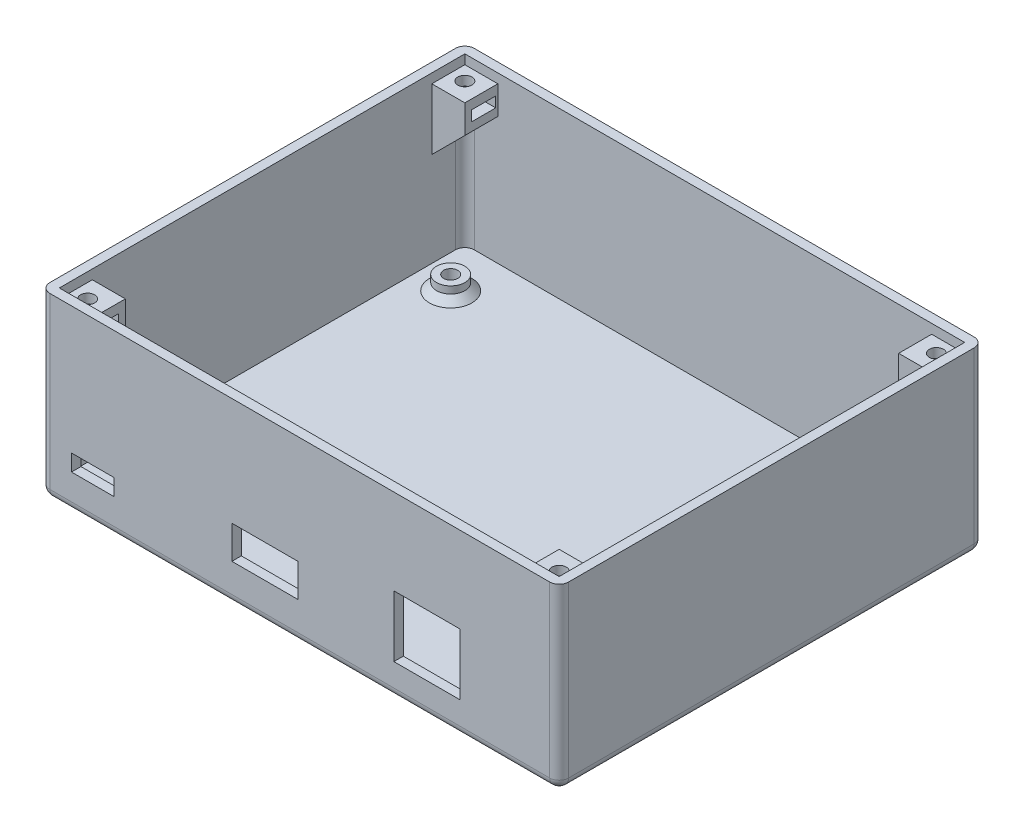
SolidWorks part; units mm, degrees
ref_plane "Front Plane" through (0, 0, 0) normal (0, 0, 1) x (1, 0, 0)
ref_plane "Top Plane" through (0, 0, 0) normal (0, 1, 0) x (1, 0, 0)
ref_plane "Right Plane" through (0, 0, 0) normal (1, 0, 0) x (0, 0, -1)
sketch "Sketch1" plane through (0, 0, 0) normal (0, 1, 0) x (1, 0, 0)
  line L1 (-55, 45) -> (55, 45)
  line L2 (-55, 45) -> (-55, -45)
  line L3 (-55, -45) -> (55, -45)
  line L4 (55, 45) -> (55, -45)
  line L5 (-55, 45) -> (55, -45) construction
  line L6 (-55, -45) -> (55, 45) construction
  point P0 (0, 0)
  dimension "D1" = 110
  dimension "D2" = 90
extrude "Boss-Extrude1" add sketch "Sketch1" along normal blind 3
sketch "Sketch2" plane through (0, 3, 0) normal (0, 1, 0) x (1, 0, 0)
  line L4 (-55, -45) -> (55, -45) construction
  line L5 (55, -45) -> (55, 45) construction
  line L6 (-55, 45) -> (-55, -45) construction
  line L7 (55, 45) -> (-55, 45) construction
  line L8 (53, -43) -> (53, 43)
  line L9 (53, 43) -> (-53, 43)
  line L10 (-53, 43) -> (-53, -43)
  line L11 (-53, -43) -> (53, -43)
  line L12 (53, -43) -> (53, 43)
  line L13 (53, 43) -> (-53, 43)
  line L14 (-53, 43) -> (-53, -43)
  line L15 (-53, -43) -> (53, -43)
  line L16 (-55, -45) -> (55, -45)
  line L17 (55, -45) -> (55, 45)
  line L18 (-55, 45) -> (-55, -45)
  line L19 (55, 45) -> (-55, 45)
  dimension "D1" = 2
extrude "Boss-Extrude2" add sketch "Sketch2" along normal blind 35
sketch "Sketch3" plane through (0, 3, 0) normal (0, 1, 0) x (1, 0, 0)
  line L0 (0, 43) -> (0, -43) construction
  line L1 (53, 43) -> (-53, 43) construction
  line L2 (-53, -43) -> (53, -43) construction
  line L3 (-53, 0) -> (53, 0) construction
  line L4 (-53, 43) -> (-53, -43) construction
  line L5 (53, -43) -> (53, 43) construction
  line L7 (-50, -42) -> (50, -42) construction
  line L8 (-50, -42) -> (-50, 37) construction
  line L9 (-50, 37) -> (50, 37) construction
  line L10 (50, -42) -> (50, 37) construction
  line L11 (-50, -42) -> (50, 37) construction
  line L12 (-50, 37) -> (50, -42) construction
  line L13 (-53, -43) -> (53, -43) construction
  circle A0 centre (-46, 33) radius 3
  circle A1 centre (40, 33) radius 3
  circle A2 centre (-46, -25) radius 3
  circle A3 centre (40, -25) radius 3
  point P12 (0, -2.5)
  dimension "D8" = 6
  dimension "D9" = 6
  dimension "D10" = 6
  dimension "D11" = 6
  dimension "D1" = 100
  dimension "D2" = 79
  dimension "D3" = 1
  dimension "D4" = 4
  dimension "D5" = 10
  dimension "D6" = 86
  dimension "D7" = 58
extrude "Boss-Extrude3" add sketch "Sketch3" along normal blind 3
sketch "Sketch4" plane through (0, 6, 0) normal (0, 1, 0) x (1, 0, 0)
  circle A0 centre (-46, 33) radius 1.5
  circle A1 centre (40, 33) radius 1.5
  circle A2 centre (40, -25) radius 1.5
  circle A3 centre (-46, -25) radius 1.5
  dimension "D1" = 3
  dimension "D2" = 3
  dimension "D3" = 3
  dimension "D4" = 3
extrude "Cut-Extrude1" cut sketch "Sketch4" against normal through all
sketch "Sketch5" plane through (0, 0, 0) normal (0, -1, 0) x (1, 0, 0)
  line L0 (37.45, 26.4722) -> (37.45, 23.5278)
  line L1 (-46, 27.9445) -> (-48.55, 26.4722)
  line L2 (-48.55, 26.4722) -> (-48.55, 23.5278)
  line L3 (-48.55, 23.5278) -> (-46, 22.0555)
  line L4 (-46, 22.0555) -> (-43.45, 23.5278)
  line L5 (-43.45, 23.5278) -> (-43.45, 26.4722)
  line L6 (-43.45, 26.4722) -> (-46, 27.9445)
  line L7 (42.55, 23.5278) -> (42.55, 26.4722)
  line L8 (42.55, 26.4722) -> (40, 27.9445)
  line L9 (37.45, 23.5278) -> (40, 22.0555)
  line L10 (40, 22.0555) -> (42.55, 23.5278)
  line L11 (40, 27.9445) -> (37.45, 26.4722)
  line L12 (-48.55, -34.4722) -> (-46, -35.9445)
  line L13 (42.55, -34.4722) -> (42.55, -31.5278)
  line L14 (40, -30.0555) -> (37.45, -31.5278)
  line L15 (-43.45, -34.4722) -> (-43.45, -31.5278)
  line L16 (-46, -30.0555) -> (-48.55, -31.5278)
  line L17 (-43.45, -31.5278) -> (-46, -30.0555)
  line L18 (37.45, -31.5278) -> (37.45, -34.4722)
  line L19 (40, -35.9445) -> (42.55, -34.4722)
  line L20 (37.45, -34.4722) -> (40, -35.9445)
  line L21 (42.55, -31.5278) -> (40, -30.0555)
  line L22 (-46, -35.9445) -> (-43.45, -34.4722)
  line L23 (-48.55, -31.5278) -> (-48.55, -34.4722)
  circle A0 centre (-46, 25) radius 2.55 construction
  dimension "D1" = 5.1
extrude "Cut-Extrude2" cut sketch "Sketch5" against normal blind 2.3
sketch "Sketch6" plane through (0, 0, 45) normal (0, 0, 1) x (1, 0, 0)
  line L0 (-43.945, 10.5162) -> (-43.895, 7.9562) construction
  line L1 (-40.805, 10.5162) -> (-47.085, 10.5162) construction
  line L2 (26.95, 18.94) -> (26.95, 7.77) construction
  line L3 (20.5, 18.94) -> (33.4, 18.94) construction
  line L4 (29.45, 7.77) -> (24.45, 7.77) construction
  line L5 (-7.4, 14.53) -> (-7.4, 8.66) construction
  line L6 (-12.95, 14.53) -> (-1.85, 14.53) construction
  line L7 (-12.95, 8.66) -> (-1.85, 8.66) construction
  line L9 (-48.42, 7.4862) -> (-39.42, 7.4862)
  line L10 (-48.42, 7.4862) -> (-48.42, 10.9862)
  line L11 (-48.42, 10.9862) -> (-39.42, 10.9862)
  line L12 (-39.42, 7.4862) -> (-39.42, 10.9862)
  line L13 (-48.42, 7.4862) -> (-39.42, 10.9862) construction
  line L14 (-48.42, 10.9862) -> (-39.42, 7.4862) construction
  line L15 (19.95, 6.855) -> (33.95, 6.855)
  line L16 (19.95, 6.855) -> (19.95, 19.855)
  line L17 (19.95, 19.855) -> (33.95, 19.855)
  line L18 (33.95, 6.855) -> (33.95, 19.855)
  line L19 (19.95, 6.855) -> (33.95, 19.855) construction
  line L20 (19.95, 19.855) -> (33.95, 6.855) construction
  line L21 (-14.4, 8.095) -> (-0.4, 8.095)
  line L22 (-14.4, 8.095) -> (-14.4, 15.095)
  line L23 (-14.4, 15.095) -> (-0.4, 15.095)
  line L24 (-0.4, 8.095) -> (-0.4, 15.095)
  line L25 (-14.4, 8.095) -> (-0.4, 15.095) construction
  line L26 (-14.4, 15.095) -> (-0.4, 8.095) construction
  point P17 (-43.92, 9.2362)
  point P22 (26.95, 13.355)
  point P27 (-7.4, 11.595)
  dimension "D1" = 9
  dimension "D2" = 3.5
  dimension "D3" = 14
  dimension "D4" = 13
  dimension "D5" = 14
  dimension "D6" = 7
extrude "Cut-Extrude3" cut sketch "Sketch6" against normal up to next
fillet "Fillet2" radius 2 8 edges at (55, 0, 0) (0, 0, 45) (-55, 0, 0) (0, 0, -45) (55, 19, -45) (55, 19, 45) (-55, 19, 45) (-55, 19, -45)
ref_plane "Plane1" through (0, 36, 0) normal (0, 1, 0) x (1, 0, 0)
sketch "Sketch7" plane through (0, 36, 0) normal (0, 1, 0) x (1, 0, 0)
  line L0 (0, 45) -> (0, -45) construction
  line L1 (53, 45) -> (-53, 45) construction
  line L2 (-53, -45) -> (53, -45) construction
  line L3 (-55, 0) -> (55, 0) construction
  line L4 (-55, 43) -> (-55, -43) construction
  line L5 (55, -43) -> (55, 43) construction
  line L6 (-53, 36) -> (-46, 36)
  line L7 (-53, 43) -> (-53, -43) construction
  line L8 (-46, 36) -> (-46, 43)
  line L9 (53, 43) -> (-53, 43) construction
  line L10 (-46, 43) -> (-53, 43)
  line L11 (-53, 43) -> (-53, 36)
  dimension "D1" = 7
  dimension "D2" = 7
extrude "Boss-Extrude4" add sketch "Sketch7" against normal blind 6
ref_plane "Plane2" through (0, 34, 0) normal (0, 1, 0) x (1, 0, 0)
sketch "Sketch8" plane through (0, 34, 0) normal (0, 1, 0) x (1, 0, 0)
  line L0 (53, 45) -> (-53, 45) construction
  line L2 (-48.5278, 42.55) -> (-51.4722, 42.55)
  line L3 (-51.4722, 42.55) -> (-52.9445, 40)
  line L4 (-52.9445, 40) -> (-51.4722, 37.45)
  line L5 (-51.4722, 37.45) -> (-48.5278, 37.45)
  line L7 (-55, 43) -> (-55, -43) construction
  line L8 (-48.5278, 42.55) -> (-46, 42.55)
  line L9 (-46, 36) -> (-46, 43) construction
  line L10 (-48.5278, 37.45) -> (-46, 37.45)
  line L11 (-46, 37.45) -> (-46, 42.55)
  line L13 (-47.0555, 40) -> (-47.7916, 41.275) [skipped]
  line L14 (-48.5278, 37.45) -> (-47.7916, 38.725) [skipped]
  circle A0 centre (-50, 40) radius 2.55 construction
  dimension "D1" = 5.1
  dimension "D2" = 5
  dimension "D3" = 5
extrude "Cut-Extrude4" cut sketch "Sketch8" against normal blind 2.2 contours L10 L11 L8 L2 L3 L4 L5
sketch "Sketch10" plane through (0, 36, 0) normal (0, 1, 0) x (1, 0, 0)
  line L0 (53, 45) -> (-53, 45) construction
  line L1 (-55, 43) -> (-55, -43) construction
  circle A0 centre (-50, 40) radius 1.5
  dimension "D1" = 3
  dimension "D2" = 5
  dimension "D3" = 5
extrude "Cut-Extrude5" cut sketch "Sketch10" against normal blind 5
chamfer "Chamfer2" distance 7 angle 45 1 edges at (-53, 30, -39.5)
mirror "Mirror3" about plane through (0, 0, 0) normal (1, 0, 0) of "Cut-Extrude5", "Cut-Extrude4", "Boss-Extrude4"
mirror "Mirror4" about plane through (0, 0, 0) normal (0, 0, 1) of "Mirror3"
chamfer "Chamfer3" distance 7 angle 45 1 edges at (53, 30, -39.5)
chamfer "Chamfer4" distance 7 angle 45 2 edges at (-53, 30, 39.5) (53, 30, 39.5)
fillet "Fillet6" radius 2 4 edges at (53, 13, 43) (53, 13, -43) (-53, 13, -43) (-53, 13, 43)
chamfer "Chamfer5" distance 1.5 angle 45 4 edges at (-46, 3, 28) (40, 3, 28) (40, 3, -30) (-46, 3, -30)
